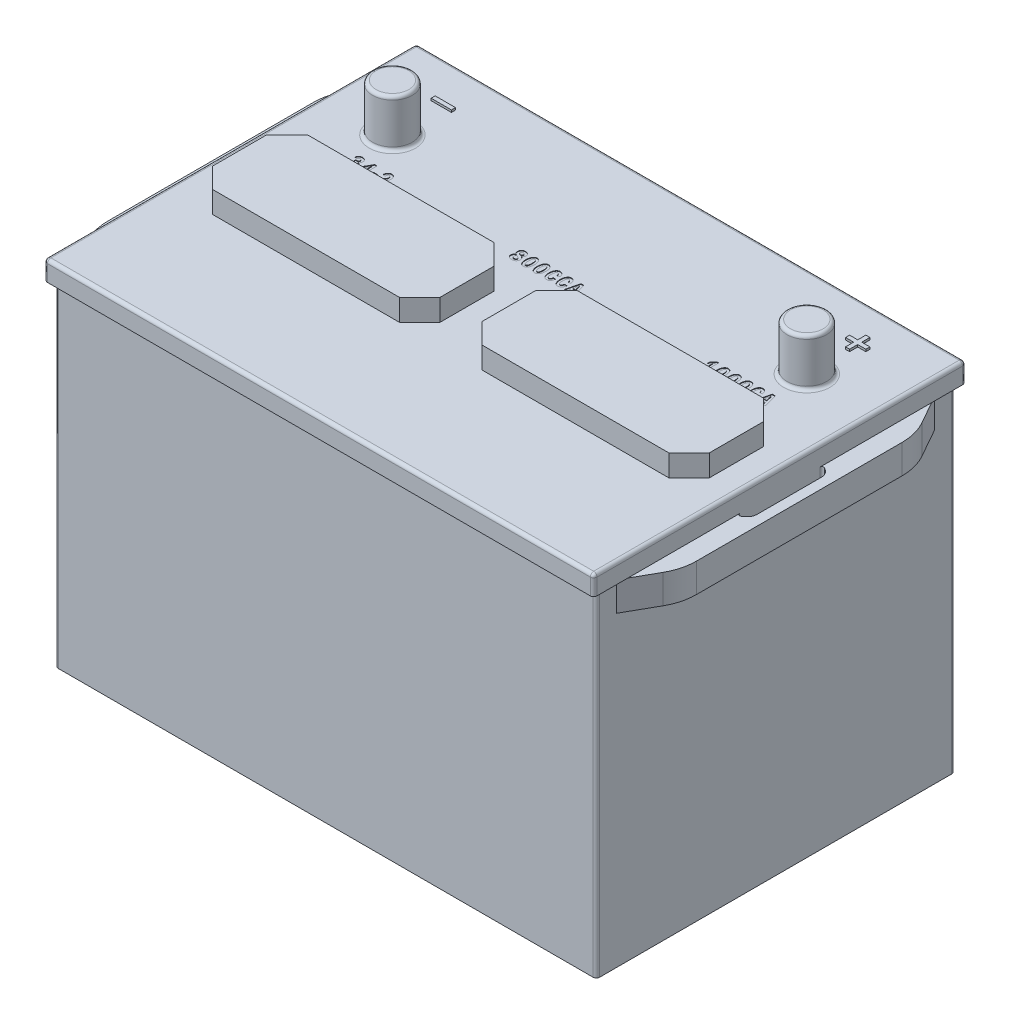
SolidWorks part; units mm, degrees
material "1060 Alloy"
ref_plane "Front Plane" through (0, 0, 0) normal (0, 0, 1) x (1, 0, 0)
ref_plane "Top Plane" through (0, 0, 0) normal (0, 1, 0) x (1, 0, 0)
ref_plane "Right Plane" through (0, 0, 0) normal (1, 0, 0) x (0, 0, -1)
sketch "Sketch1" plane through (0, 0, 0) normal (0, 1, 0) x (1, 0, 0)
  line L1 (-127, 84.1375) -> (127, 84.1375)
  line L2 (-127, 84.1375) -> (-127, -84.1375)
  line L3 (-127, -84.1375) -> (127, -84.1375)
  line L4 (127, 84.1375) -> (127, -84.1375)
  line L5 (-127, 84.1375) -> (127, -84.1375) construction
  line L6 (-127, -84.1375) -> (127, 84.1375) construction
  point P0 (0, 0)
  dimension "D1" = 254
  dimension "D2" = 168.275
extrude "Boss-Extrude1" add sketch "Sketch1" along normal blind 157.48
sketch "Sketch2" plane through (0, 157.48, 0) normal (0, 1, 0) x (1, 0, 0)
  line L1 (-128.905, 87.3125) -> (128.905, 87.3125)
  line L2 (-128.905, 87.3125) -> (-128.905, -87.3125)
  line L3 (-128.905, -87.3125) -> (128.905, -87.3125)
  line L4 (128.905, 87.3125) -> (128.905, -87.3125)
  line L5 (-128.905, 87.3125) -> (128.905, -87.3125) construction
  line L6 (-128.905, -87.3125) -> (128.905, 87.3125) construction
  point P0 (0, 0)
  dimension "D1" = 257.81
  dimension "D2" = 174.625
extrude "Boss-Extrude5" add sketch "Sketch2" along normal blind 9.2075
sketch "Sketch3" plane through (0, 166.6875, 0) normal (0, 1, 0) x (1, 0, 0)
  line L0 (-97.2026, 44.3865) -> (97.2026, 44.3865) construction
  line L1 (0, 44.3865) -> (0, 0) construction
  line L2 (128.905, 87.3125) -> (-128.905, 87.3125) construction
  circle A0 centre (-97.2026, 44.3865) radius 9.271
  circle A1 centre (97.2026, 44.3865) radius 9.271
  dimension "D1" = 18.542
  dimension "D2" = 194.4053
  dimension "D3" = 33.655
extrude "Boss-Extrude6" add sketch "Sketch3" along normal blind 22.225
sketch "Sketch4" plane through (0, 166.6875, 0) normal (0, 1, 0) x (1, 0, 0)
  line L0 (0, 36.0927) -> (0, -46.2559) construction
  line L1 (-128.905, -87.3125) -> (128.905, -87.3125) construction
  line L2 (-116.5225, -30.1625) -> (-9.8425, -30.1625)
  line L3 (-116.5225, -30.1625) -> (-116.5225, 14.2875)
  line L4 (-116.5225, 14.2875) -> (-9.8425, 14.2875)
  line L5 (-9.8425, -30.1625) -> (-9.8425, 14.2875)
  line L6 (-116.5225, -30.1625) -> (-9.8425, 14.2875) construction
  line L7 (-116.5225, 14.2875) -> (-9.8425, -30.1625) construction
  line L8 (9.8425, -30.1625) -> (116.5225, -30.1625)
  line L9 (9.8425, -30.1625) -> (9.8425, 14.2875)
  line L10 (9.8425, 14.2875) -> (116.5225, 14.2875)
  line L11 (116.5225, -30.1625) -> (116.5225, 14.2875)
  line L12 (9.8425, -30.1625) -> (116.5225, 14.2875) construction
  line L13 (9.8425, 14.2875) -> (116.5225, -30.1625) construction
  point P3 (-63.1825, -7.9375)
  point P8 (63.1825, -7.9375)
  dimension "D1" = 44.45
  dimension "D2" = 106.68
  dimension "D3" = 19.685
  dimension "D4" = 57.15
extrude "Boss-Extrude7" add sketch "Sketch4" along normal blind 10.16
chamfer "Chamfer1" distance 9.525 angle 45 8 edges at (116.5225, 171.7675, 30.1625) (116.5225, 171.7675, -14.2875) (-9.8425, 171.7675, 30.1625) (9.8425, 171.7675, 30.1625) (9.8425, 171.7675, -14.2875) (-9.8425, 171.7675, -14.2875) (-116.5225, 171.7675, 30.1625) (-116.5225, 171.7675, -14.2875)
sketch "Sketch5" plane through (0, 157.48, 0) normal (0, -1, 0) x (1, 0, 0)
  line L0 (-127, -74.6125) -> (-134.8314, -60.7397)
  line L2 (-138.1125, -48.2532) -> (-138.1125, 48.2532)
  line L3 (-134.8314, 60.7397) -> (-127, 74.6125)
  line L4 (-127, -84.1375) -> (-127, 84.1375) construction
  line L5 (0, -49.3831) -> (0, 48.0801) construction
  line L6 (128.905, 0) -> (-128.905, 0) construction
  line L7 (-127, -84.1375) -> (-127, 84.1375) construction
  line L8 (134.8314, 60.7397) -> (127, 74.6125)
  line L9 (138.1125, -48.2532) -> (138.1125, 48.2532)
  line L10 (127, -74.6125) -> (134.8314, -60.7397)
  line L11 (-127, 74.6125) -> (-127, -74.6125)
  line L12 (127, 74.6125) -> (127, -74.6125)
  arc A0 (134.8314, 60.7397) -> (138.1125, 48.2532) centre (112.7125, 48.2532) cw
  arc A1 (138.1125, -48.2532) -> (134.8314, -60.7397) centre (112.7125, -48.2532) cw
  arc A2 (-138.1125, 48.2532) -> (-134.8314, 60.7397) centre (-112.7125, 48.2532) cw
  arc A3 (-134.8314, -60.7397) -> (-138.1125, -48.2532) centre (-112.7125, -48.2532) cw
  point P13 (0, 0)
  point P19 (138.1125, 54.9275)
  point P22 (138.1125, -54.9275)
  point P25 (-138.1125, 54.9275)
  point P28 (-138.1125, -54.9275)
  dimension "D4" = 25.4
  dimension "D1" = 149.225
  dimension "D2" = 276.225
  dimension "D3" = 109.855
sketch "Sketch6" plane through (0, 166.6875, 0) normal (0, 1, 0) x (1, 0, 0)
  line L0 (97.2026, 73.025) -> (97.2026, 63.5)
  line L1 (92.4401, 68.2625) -> (101.9651, 68.2625)
  line L2 (-101.9651, 68.2625) -> (-92.4401, 68.2625)
  line L3 (-97.2026, 44.3865) -> (-97.2026, 68.2625) construction
  line L4 (97.2026, 44.3865) -> (97.2026, 63.5) construction
  line L5 (128.905, 87.3125) -> (-128.905, 87.3125) construction
  point P10 (97.2026, 68.2625)
  dimension "D1" = 9.525
  dimension "D2" = 19.05
extrude "Extrude-Thin1" add sketch "Sketch6" along normal blind 1.016 thin thin type mid plane wall 1.905
extrude "Boss-Extrude9" add sketch "Sketch5" along normal blind 13.589 contours L8 L12 L10 A1 L9 A0 | L2 A2 L3 L11 L0 A3
sketch "Sketch7" plane through (0, 166.6875, 0) normal (0, 1, 0) x (1, 0, 0)
  line L0 (-97.2026, 21.7771) -> (97.2026, 21.7771) construction
  line L1 (97.2026, 21.7771) -> (97.2026, 44.3865) construction
  line L2 (-97.2026, 44.3865) -> (-97.2026, 21.7771) construction
  text T0 "<b>34-2                    800CCA                    1000CA</b>" font "Franklin Gothic Medium" height 6.35
extrude "IDENTIFICATION" cut sketch "Sketch7" against normal blind 0.254
fillet "Fillet1" radius 1.5875 18 edges at (-128.905, 166.6875, 0) (0, 166.6875, -87.3125) (128.905, 166.6875, 0) (0, 166.6875, 87.3125) (-128.905, 162.0838, -87.3125) (128.905, 162.0838, -87.3125) (-128.905, 162.0838, 87.3125) (128.905, 162.0838, 87.3125) (127, 78.74, -84.1375) (127, 78.74, 84.1375) (-127, 78.74, -84.1375) (-127, 78.74, 84.1375) (127, 157.48, -79.375) (-127, 157.48, -79.375) (-127, 157.48, 79.375) (127, 157.48, 79.375) (0, 157.48, -84.1375) (0, 157.48, 84.1375)
fillet "Fillet2" radius 1.5875 4 edges at (97.2026, 188.9125, -35.1155) (-97.2026, 188.9125, -35.1155) (-97.2026, 166.6875, -35.1155) (97.2026, 166.6875, -35.1155)
sketch "Sketch8" plane through (0, 157.48, 0) normal (0, 1, 0) x (1, 0, 0)
  line L0 (-133.35, 15.0116) -> (-133.35, -15.0116)
  line L2 (-131.3556, -18.887) -> (-130.3107, -19.6334)
  line L3 (-128.905, -18.91) -> (-128.905, 18.91)
  line L4 (-130.3107, 19.6334) -> (-131.3556, 18.887)
  line L5 (-128.905, 71.2379) -> (-128.905, -71.2379) construction
  line L6 (-133.35, 0) -> (-128.905, 0) construction
  line L8 (0, 0) -> (0, 57.5932) construction
  line L9 (133.35, 0) -> (128.905, 0) construction
  line L10 (130.3107, 19.6334) -> (131.3556, 18.887)
  line L11 (128.905, -18.91) -> (128.905, 18.91)
  line L12 (131.3556, -18.887) -> (130.3107, -19.6334)
  line L13 (133.35, 15.0116) -> (133.35, -15.0116)
  line L14 (-138.1125, 48.2532) -> (-138.1125, -48.2532) construction
  arc A0 (131.3556, -18.887) -> (133.35, -15.0116) centre (128.5875, -15.0116) ccw
  arc A1 (131.3556, 18.887) -> (133.35, 15.0116) centre (128.5875, 15.0116) cw
  arc A2 (-133.35, -15.0116) -> (-131.3556, -18.887) centre (-128.5875, -15.0116) ccw
  arc A3 (-133.35, 15.0116) -> (-131.3556, 18.887) centre (-128.5875, 15.0116) cw
  arc A4 (128.905, -18.91) -> (130.3107, -19.6334) centre (129.794, -18.91) ccw
  arc A5 (130.3107, 19.6334) -> (128.905, 18.91) centre (129.794, 18.91) ccw
  arc A6 (-130.3107, -19.6334) -> (-128.905, -18.91) centre (-129.794, -18.91) ccw
  arc A7 (-128.905, 18.91) -> (-130.3107, 19.6334) centre (-129.794, 18.91) ccw
  point P21 (133.35, -17.4625)
  point P24 (133.35, 17.4625)
  point P27 (-133.35, -17.4625)
  point P30 (-133.35, 17.4625)
  point P33 (128.905, -20.6375)
  point P36 (128.905, 20.6375)
  point P39 (-128.905, -20.6375)
  point P42 (-128.905, 20.6375)
  dimension "D4" = 4.7625
  dimension "D5" = 0.889
  dimension "D1" = 41.275
  dimension "D2" = 34.925
  dimension "D3" = 4.7625
extrude "Cut-Extrude1" cut sketch "Sketch8" against normal up to next
